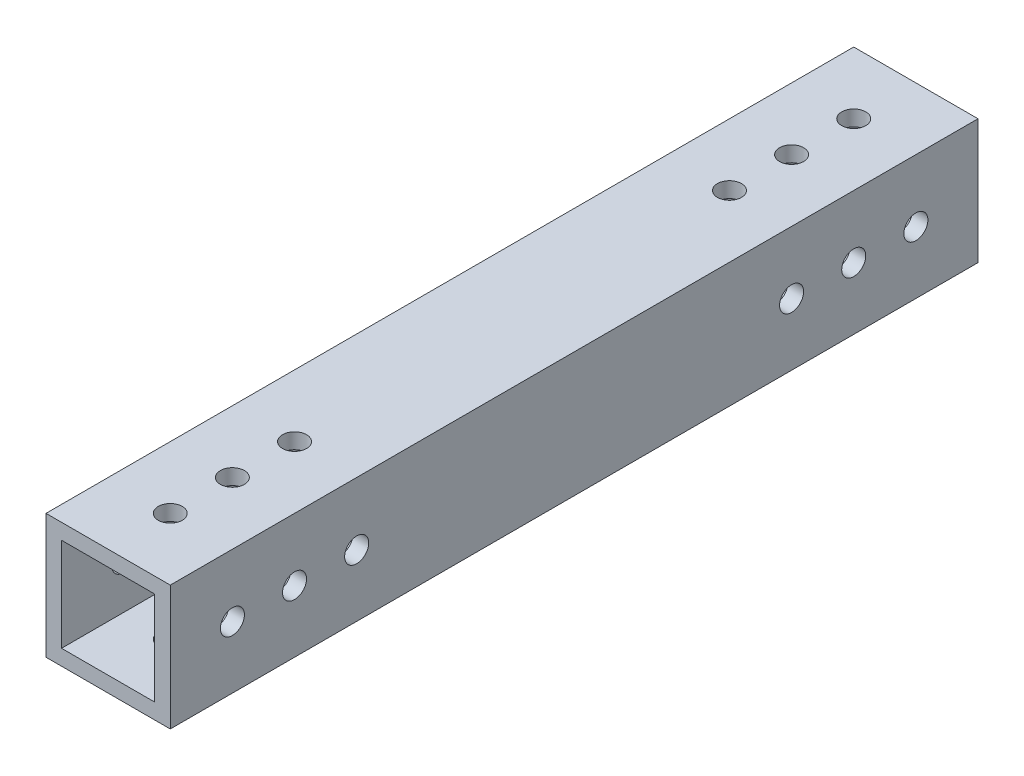
SolidWorks part; units mm, degrees
ref_plane "Front Plane" through (0, 0, 0) normal (0, 0, 1) x (1, 0, 0)
ref_plane "Top Plane" through (0, 0, 0) normal (0, 1, 0) x (1, 0, 0)
ref_plane "Right Plane" through (0, 0, 0) normal (1, 0, 0) x (0, 0, -1)
sketch "Sketch1" plane through (0, 0, 0) normal (0, 0, 1) x (1, 0, 0)
  line L1 (0, 0) -> (-25.4, 0)
  line L2 (0, 0) -> (0, 25.4756)
  line L3 (0, 25.4756) -> (-25.4, 25.4756)
  line L4 (-25.4, 0) -> (-25.4, 25.4756)
  dimension "D1" = 25.4
  dimension "D2" = 25.4756
extrude "Extrude-Thin1" add sketch "Sketch1" along normal blind 165.1 thin thin type one direction reverse wall 3.175
hole_wizard "#10 (0.1935) Diameter Hole1" positions "Sketch2" profile "Sketch3" hole size "#10" standard "ANSI Inch" end condition through all
sketch "Sketch2" plane through (0, 0, 0) normal (0, -1, 0) x (-1, 0, 0)
  line L0 (25.4, -165.1) -> (0, -165.1) construction
  line L1 (25.4, -165.1) -> (25.4, 0) construction
  line L2 (25.4, 0) -> (0, 0) construction
  point P0 (12.7, -25.4)
  point P2 (12.7, -12.7)
  point P4 (12.7, -38.1)
  point P6 (12.7, -127)
  point P8 (12.7, -139.7)
  point P10 (12.7, -152.4)
  dimension "D1" = 12.7
  dimension "D2" = 12.7
  dimension "D3" = 12.7
  dimension "D4" = 12.7
  dimension "D5" = 12.7
  dimension "D6" = 12.7
  dimension "D7" = 12.7
  dimension "D8" = 12.7
sketch "Sketch3" plane through (-12.7, 0, 25.4) normal (1, 0, 0) x (0, 0, -1)
  line L0 (0, 0) -> (0, 25.4756)
  line L1 (0, 25.4756) -> (2.4574, 25.4756)
  line L2 (2.4574, 25.4756) -> (2.4574, 0)
  line L5 (2.4574, 0) -> (0, 0)
  line L11 (0, -6.35) -> (0, 107.95) construction
  dimension "Thru Hole Dia." = 4.9149
  dimension "Thru Hole Depth" = 25.4756
hole_wizard "#10 (0.1935) Diameter Hole2" positions "Sketch4" profile "Sketch5" hole size "#10" standard "ANSI Inch" end condition through all
sketch "Sketch4" plane through (-25.4, 0, 0) normal (-1, 0, 0) x (0, 0, 1)
  line L0 (0, 3.175) -> (0, 22.3006) construction
  line L1 (165.1, 0) -> (0, 0) construction
  line L3 (165.1, 25.4756) -> (165.1, 0) construction
  line L4 (165.1, 25.4756) -> (0, 25.4756) construction
  point P0 (152.4, 12.6667)
  point P2 (139.7, 12.6667)
  point P4 (127, 12.6667)
  point P6 (38.1, 12.7)
  point P8 (25.4, 12.7)
  point P10 (12.7, 12.7)
  dimension "D1" = 12.7
  dimension "D2" = 12.7
  dimension "D3" = 12.7
  dimension "D4" = 12.7
  dimension "D5" = 12.7
  dimension "D6" = 12.7
  dimension "D7" = 12.8089
  dimension "D8" = 12.7
sketch "Sketch5" plane through (-25.4, 12.6667, 152.4) normal (0, 1, 0) x (0, 0, 1)
  line L0 (0, 0) -> (0, 25.4)
  line L1 (0, 25.4) -> (2.4574, 25.4)
  line L2 (2.4574, 25.4) -> (2.4574, 0)
  line L5 (2.4574, 0) -> (0, 0)
  line L11 (0, -6.35) -> (0, 107.95) construction
  dimension "Thru Hole Dia." = 4.9149
  dimension "Thru Hole Depth" = 25.4
